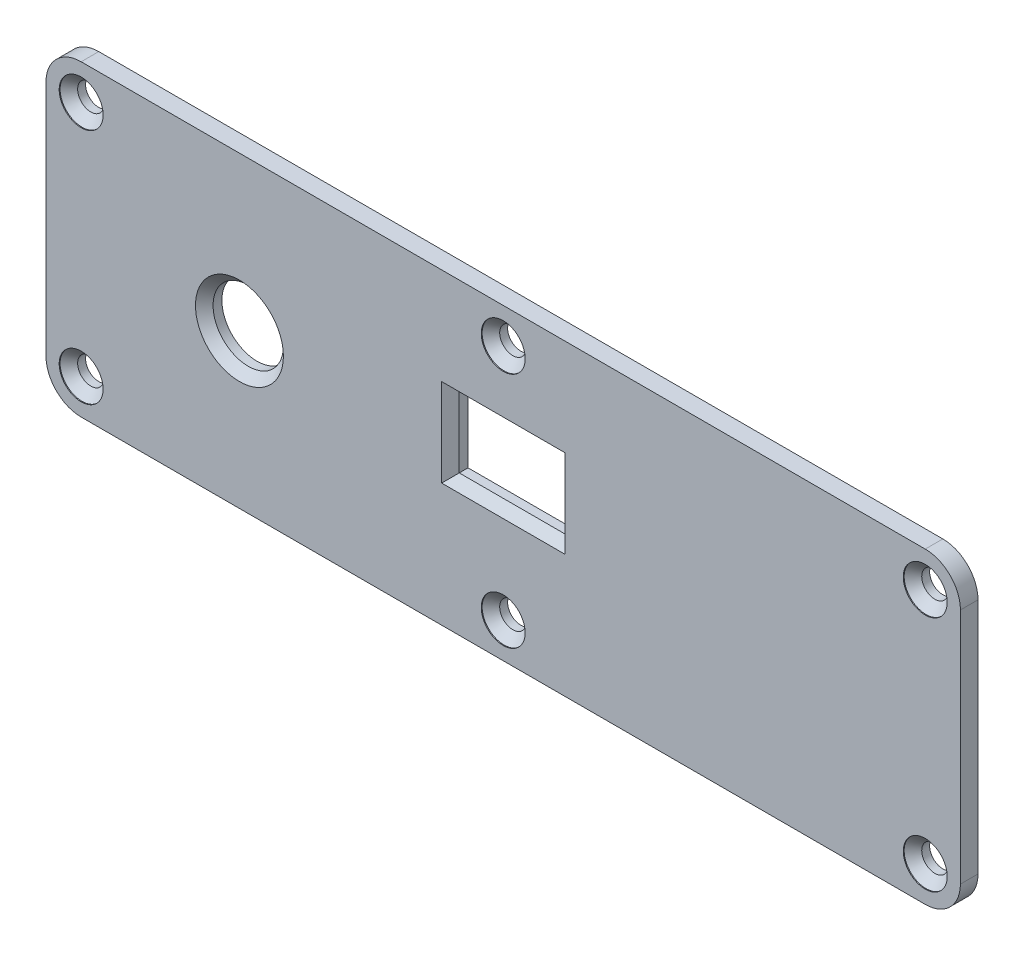
SolidWorks part; units mm, degrees
ref_plane "Ön Düzlem" through (0, 0, 0) normal (0, 0, 1) x (1, 0, 0)
ref_plane "Üst Düzlem" through (0, 0, 0) normal (0, 1, 0) x (1, 0, 0)
ref_plane "Sağ Düzlem" through (0, 0, 0) normal (1, 0, 0) x (0, 0, -1)
sketch "Çizim1" plane through (0, 0, 0) normal (0, 0, 1) x (1, 0, 0)
  line L1 (0, 0) -> (-104, 0)
  line L2 (0, 0) -> (0, 35)
  line L3 (0, 35) -> (-104, 35)
  line L4 (-104, 0) -> (-104, 35)
  dimension "D1" = 104
  dimension "D2" = 35
extrude "Yükseklik-Ekstrüzyon1" add sketch "Çizim1" along normal blind 2
sketch "Çizim2" plane through (0, 0, 2) normal (0, 0, 1) x (1, 0, 0)
  line L0 (0, 35) -> (-104, 35) construction
  line L1 (-104, 35) -> (-104, 0) construction
  line L2 (-104, 0) -> (0, 0) construction
  line L3 (-52, 35) -> (-52, 0) construction
  circle A0 centre (-100, 31) radius 1.5
  circle A1 centre (-100, 4) radius 1.5
  circle A2 centre (-4, 4) radius 1.5
  circle A3 centre (-4, 31) radius 1.5
  dimension "D1" = 3
  dimension "D2" = 3
  dimension "D3" = 4
  dimension "D4" = 4
  dimension "D5" = 27
  dimension "D6" = 4
  dimension "D7" = 4
extrude "Kes-Ekstrüzyon1" cut sketch "Çizim2" against normal blind 2
sketch "Çizim3" plane through (0, 0, 2) normal (0, 0, 1) x (1, 0, 0)
  line L0 (-52, 35) -> (-52, 0) construction
  line L1 (0, 35) -> (-104, 35) construction
  line L2 (-104, 0) -> (0, 0) construction
  circle A0 centre (-100, 31) radius 2.5
  circle A1 centre (-100, 4) radius 2.5
  circle A2 centre (-4, 4) radius 2.5
  circle A3 centre (-4, 31) radius 2.5
  dimension "D1" = 5
  dimension "D2" = 5
extrude "Kes-Ekstrüzyon2" cut sketch "Çizim3" against normal blind 0.1
chamfer "Pah2" distance 1 angle 45 4 edges at (-5.5, 4, 1.9) (-5.5, 31, 1.9) (-98.5, 4, 1.9) (-98.5, 31, 1.9)
sketch "Çizim4" plane through (0, 0, 2) normal (0, 0, 1) x (1, 0, 0)
  line L0 (0, 35) -> (-104, 35) construction
  line L2 (-104, 35) -> (-104, 0) construction
  circle A0 centre (-52, 31) radius 1.5
  circle A1 centre (-52, 4) radius 1.5
  dimension "D1" = 3
  dimension "D2" = 3
  dimension "D3" = 27
  dimension "D4" = 4
  dimension "D5" = 52
  dimension "D6" = 52
extrude "Kes-Ekstrüzyon3" cut sketch "Çizim4" against normal blind 2
sketch "Çizim5" plane through (0, 0, 2) normal (0, 0, 1) x (1, 0, 0)
  circle A0 centre (-52, 31) radius 2.5
  circle A1 centre (-52, 4) radius 2.5
  dimension "D1" = 5
  dimension "D2" = 5
extrude "Kes-Ekstrüzyon4" cut sketch "Çizim5" against normal blind 0.1
chamfer "Pah3" distance 1 angle 45 2 edges at (-50.5, 4, 1.9) (-50.5, 31, 1.9)
fillet "Radyus1" radius 4 4 edges at (0, 0, 1) (0, 35, 1) (-104, 0, 1) (-104, 35, 1)
sketch "Çizim6" plane through (0, 0, 2) normal (0, 0, 1) x (1, 0, 0)
  line L0 (-4, 35) -> (-100, 35) construction
  line L1 (-104, 31) -> (-104, 4) construction
  line L3 (-58, 23) -> (-46, 23)
  line L4 (-58, 23) -> (-58, 15)
  line L5 (-58, 15) -> (-46, 15)
  line L6 (-46, 23) -> (-46, 15)
  circle A0 centre (-82, 17.5) radius 4
  dimension "D3" = 8
  dimension "D1" = 17.5
  dimension "D2" = 22
  dimension "D4" = 12
  dimension "D5" = 8
  dimension "D6" = 12
  dimension "D7" = 46
extrude "Kes-Ekstrüzyon5" cut sketch "Çizim6" against normal blind 2
chamfer "Pah4" distance 1 angle 45 4 edges at (-46, 19, 2) (-52, 15, 2) (-58, 19, 2) (-52, 23, 2)
chamfer "Pah5" distance 1 angle 45 1 edges at (-78, 17.5, 2)
